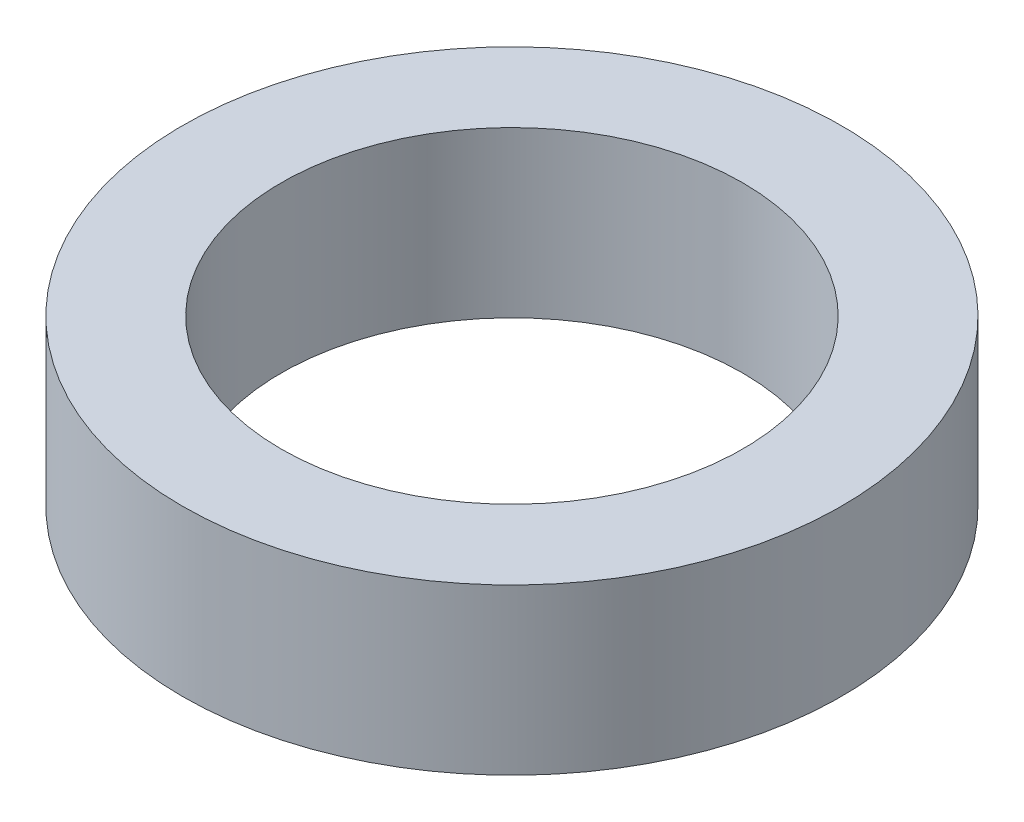
SolidWorks part; units mm, degrees
ref_plane "Front Plane" through (0, 0, 0) normal (0, 0, 1) x (1, 0, 0)
ref_plane "Top Plane" through (0, 0, 0) normal (0, 1, 0) x (1, 0, 0)
ref_plane "Right Plane" through (0, 0, 0) normal (1, 0, 0) x (0, 0, -1)
sketch "Sketch1" plane through (0, 0, 0) normal (0, 1, 0) x (1, 0, 0)
  circle A0 centre (0, 0) radius 50
  dimension "FLANGE_OD" = 100
extrude "Boss-Extrude1" add sketch "Sketch1" along normal blind 25
sketch "Sketch2" plane through (0, 0, 0) normal (0, 1, 0) x (1, 0, 0)
  circle A0 centre (0, 0) radius 35
  dimension "BORE_D" = 70
extrude "Cut-Extrude1" cut sketch "Sketch2" along normal through all
sketch "Sketch3" plane through (0, 25, 0) normal (0, 1, 0) x (1, 0, 0)
  circle A0 centre (0, 0) radius 19.0514 construction
  circle A1 centre (-19.0514, 0) radius 1.8796
  dimension "BOLT_D" = 3.7591
  dimension "BOLT_PCD" = 38.1028
extrude "Cut-Extrude2" cut sketch "Sketch3" against normal blind 21.2642 rebuild error yes
pattern_circular "CirPattern1" count 4 over 360 rebuild error yes
